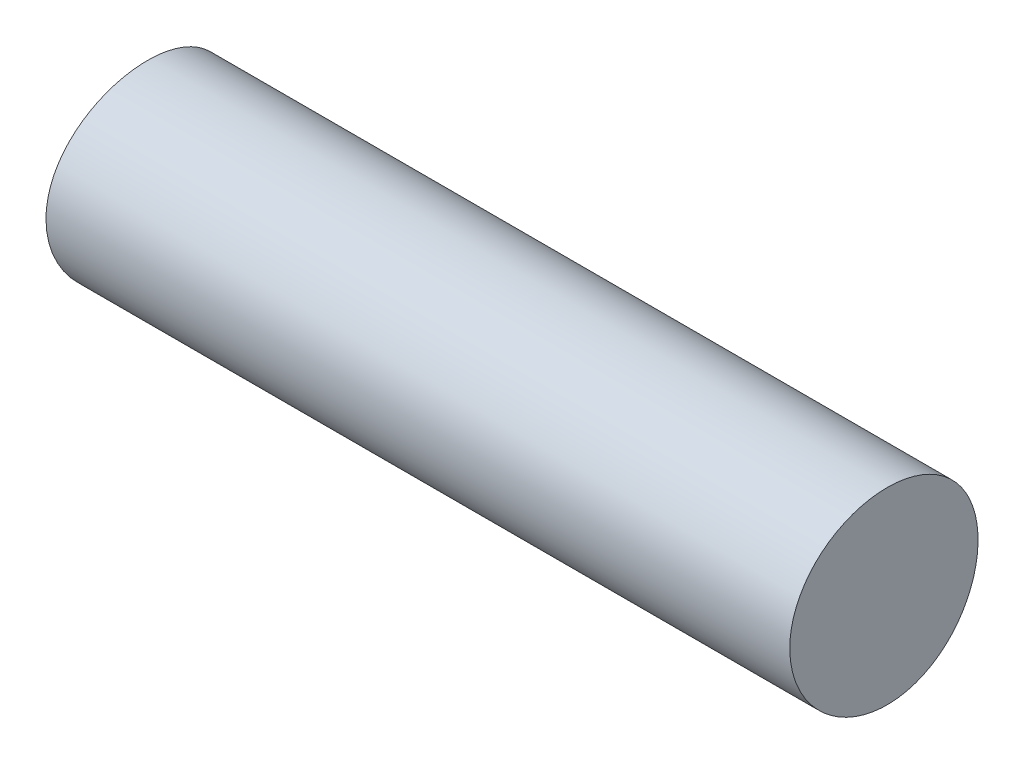
SolidWorks part; units mm, degrees
ref_plane "Front Plane" through (0, 0, 0) normal (0, 0, 1) x (1, 0, 0)
ref_plane "Top Plane" through (0, 0, 0) normal (0, 1, 0) x (1, 0, 0)
ref_plane "Right Plane" through (0, 0, 0) normal (1, 0, 0) x (0, 0, -1)
sketch "Sketch1" plane through (0, 0, 0) normal (0, 1, 0) x (1, 0, 0)
  circle A0 centre (0, 0) radius 22.5
  circle A1 centre (0, 0) radius 50
  dimension "D1" = 45
  dimension "D2" = 100
ref_plane "Plane1" through (10, 0, 0) normal (1, 0, 0) x (0, 0, -1)
sketch "Sketch2" plane through (10, 0, 0) normal (1, 0, 0) x (0, 0, -1)
  circle A0 centre (0, 4.9046) radius 3.5
extrude "Boss-Extrude6" add sketch "Sketch1" along normal blind 10
extrude "Boss-Extrude7" add sketch "Sketch2" along normal blind 100 separate body contours A0
combine bodies "Combine1" operation type common bodies to combine 106 107
